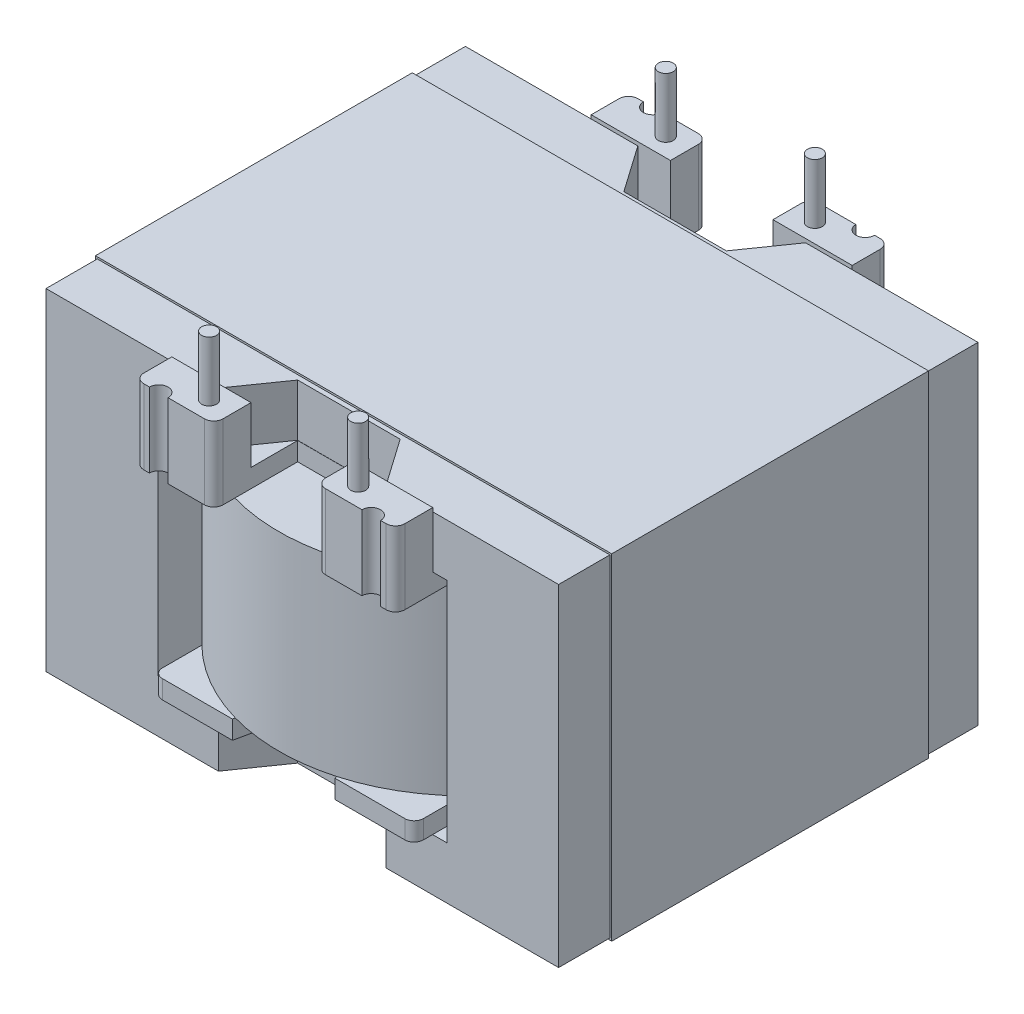
SolidWorks part; units mm, degrees
ref_plane "Спереди" through (0, 0, 0) normal (0, 0, 1) x (1, 0, 0)
ref_plane "Сверху" through (0, 0, 0) normal (0, 1, 0) x (1, 0, 0)
ref_plane "Справа" through (0, 0, 0) normal (1, 0, 0) x (0, 0, -1)
sketch "Эскиз1" plane through (0, 0, 0) normal (0, 1, 0) x (1, 0, 0)
  line L1 (-13.75, -11.25) -> (13.75, -11.25)
  line L2 (-13.75, -11.25) -> (-13.75, 11.25)
  line L3 (-13.75, 11.25) -> (13.75, 11.25)
  line L4 (13.75, -11.25) -> (13.75, 11.25)
  line L5 (-13.75, -11.25) -> (13.75, 11.25) construction
  line L6 (-13.75, 11.25) -> (13.75, -11.25) construction
  point P0 (0, 0)
  dimension "D1" = 27.5
  dimension "D2" = 22.5
extrude "Бобышка-Вытянуть1" add sketch "Эскиз1" along normal blind 17.8
sketch "Эскиз3" plane through (0, 0, 0) normal (0, 0, 1) x (1, 0, 0)
  line L0 (13.75, 17.8) -> (13.75, 0) construction
  line L1 (-7.75, 15) -> (7.75, 15)
  line L2 (-7.75, 15) -> (-7.75, 2.8)
  line L3 (-7.75, 2.8) -> (7.75, 2.8)
  line L4 (7.75, 15) -> (7.75, 2.8)
  line L5 (-7.75, 15) -> (7.75, 2.8) construction
  line L6 (-7.75, 2.8) -> (7.75, 15) construction
  line L7 (13.75, 0) -> (-13.75, 0) construction
  point P0 (0, 8.9)
  point P11 (13.75, 8.9)
  dimension "D1" = 2.8
  dimension "D2" = 15.5
extrude "Вырез-Вытянуть1" cut sketch "Эскиз3" against normal through all both and the other way through all
sketch "Эскиз4" plane through (0, 0, 0) normal (0, 1, 0) x (1, 0, 0)
  line L0 (-4.5, 11.25) -> (-2.75, 8.75)
  line L1 (13.75, 11.25) -> (-13.75, 11.25) construction
  line L2 (-2.75, 8.75) -> (2.75, 8.75)
  line L3 (2.75, 8.75) -> (4.5, 11.25)
  line L4 (4.5, 11.25) -> (-4.5, 11.25)
  line L5 (-18.0038, 0) -> (17.3641, 0) construction
  line L6 (4.5, -11.25) -> (-4.5, -11.25)
  line L7 (2.75, -8.75) -> (4.5, -11.25)
  line L8 (-2.75, -8.75) -> (2.75, -8.75)
  line L9 (-4.5, -11.25) -> (-2.75, -8.75)
  point P4 (0, 8.75)
  point P7 (0, 11.25)
  dimension "D1" = 9
  dimension "D2" = 2.5
  dimension "D3" = 5.5
extrude "Вырез-Вытянуть2" cut sketch "Эскиз4" along normal through all
ref_plane "Плоскость1" through (0, 8.9, 0) normal (0, 1, 0) x (1, 0, 0)
sketch "Эскиз2" plane through (0, 8.9, 0) normal (0, 1, 0) x (1, 0, 0)
  line L0 (0, -2.5) -> (0, 2.5) construction
  line L1 (-10, -2.5) -> (-10, 2.5)
  line L2 (10, -2.5) -> (10, 2.5)
  arc A0 (-10, -2.5) -> (10, -2.5) centre (0, -2.5) ccw
  arc A1 (10, 2.5) -> (-10, 2.5) centre (0, 2.5) ccw
  point P3 (0, 0)
  dimension "D2" = 25
  dimension "D1" = 20
extrude "Бобышка-Вытянуть2" add sketch "Эскиз2" against normal offset from surface 1 and the other way offset from surface 1 up to face at (0, 2.8, 0) other way up to face at (0, 15, 0)
sketch "Эскиз5" plane through (0, 3.8, 0) normal (0, -1, 0) x (1, 0, 0)
  line L0 (7, 11.75) -> (7, -11.75)
  line L1 (6.5, -12.25) -> (2.75, -12.25)
  line L2 (2.75, -12.25) -> (2.0847, -9.1452)
  line L3 (1.5958, -8.75) -> (-1.5958, -8.75)
  line L4 (-2.0847, -9.1452) -> (-2.75, -12.25)
  line L5 (-2.75, -12.25) -> (-6.5, -12.25)
  line L6 (-7, -11.75) -> (-7, 11.75)
  line L10 (7, 0) -> (-7, 0) construction
  line L12 (-2.75, -8.75) -> (2.75, -8.75) construction
  line L13 (-4.5, -11.25) -> (-13.75, -11.25) construction
  line L14 (-2.75, 12.25) -> (-6.5, 12.25)
  line L15 (-2.0847, 9.1452) -> (-2.75, 12.25)
  line L16 (1.5958, 8.75) -> (-1.5958, 8.75)
  line L17 (2.75, 12.25) -> (2.0847, 9.1452)
  line L18 (6.5, 12.25) -> (2.75, 12.25)
  arc A0 (2.0847, -9.1452) -> (1.5958, -8.75) centre (1.5958, -9.25) ccw
  arc A1 (-1.5958, -8.75) -> (-2.0847, -9.1452) centre (-1.5958, -9.25) ccw
  arc A2 (7, -11.75) -> (6.5, -12.25) centre (6.5, -11.75) cw
  arc A3 (-6.5, -12.25) -> (-7, -11.75) centre (-6.5, -11.75) cw
  arc A4 (-6.5, 12.25) -> (-7, 11.75) centre (-6.5, 11.75) ccw
  arc A5 (7, 11.75) -> (6.5, 12.25) centre (6.5, 11.75) ccw
  arc A6 (-1.5958, 8.75) -> (-2.0847, 9.1452) centre (-1.5958, 9.25) cw
  arc A7 (2.0847, 9.1452) -> (1.5958, 8.75) centre (1.5958, 9.25) cw
  point P0 (0, -8.75)
  point P18 (2, -8.75)
  point P21 (-2, -8.75)
  point P40 (-2, 8.75)
  point P41 (2, 8.75)
  dimension "D5" = 0.5
  dimension "D1" = 5.5
  dimension "D2" = 4
  dimension "D3" = 1
  dimension "D4" = 14
extrude "Бобышка-Вытянуть3" add sketch "Эскиз5" along normal offset from surface (0.99 mm away) 0.01 up to face at (0, 2.8, 0)
sketch "Эскиз6" plane through (0, 14, 0) normal (0, 1, 0) x (1, 0, 0)
  line L0 (-7, -12.75) -> (-7, 12.75)
  line L1 (-7, 9.6414) -> (-7, 11.75) construction
  line L2 (-6.5, 13.25) -> (-6.2, 13.25)
  line L3 (-2.75, 12.75) -> (-2.75, 8.75)
  line L4 (-2.75, 8.75) -> (2.75, 8.75)
  line L5 (2.75, 8.75) -> (2.75, 12.75)
  line L6 (3.25, 13.25) -> (5.2, 13.25)
  line L7 (7, 12.75) -> (7, -12.75)
  line L8 (7, 0) -> (-7, 0) construction
  line L9 (13.75, 11.25) -> (4.5, 11.25) construction
  line L10 (-1.5958, 8.75) -> (1.5958, 8.75) construction
  line L11 (0, 8.75) -> (0, -8.75) construction
  line L12 (-5.2, 13.25) -> (-3.25, 13.25)
  line L13 (6.2, 13.25) -> (6.5, 13.25)
  line L14 (6.2, -13.25) -> (6.5, -13.25)
  line L15 (-5.2, -13.25) -> (-3.25, -13.25)
  line L16 (3.25, -13.25) -> (5.2, -13.25)
  line L17 (2.75, -8.75) -> (2.75, -12.75)
  line L18 (-2.75, -8.75) -> (2.75, -8.75)
  line L19 (-2.75, -12.75) -> (-2.75, -8.75)
  line L20 (-6.5, -13.25) -> (-6.2, -13.25)
  arc A0 (-6.2, 13.25) -> (-5.2, 13.25) centre (-5.7, 13.25) ccw
  arc A1 (6.2, 13.25) -> (5.2, 13.25) centre (5.7, 13.25) cw
  arc A2 (-3.25, 13.25) -> (-2.75, 12.75) centre (-3.25, 12.75) cw
  arc A3 (-7, 12.75) -> (-6.5, 13.25) centre (-6.5, 12.75) cw
  arc A4 (6.5, 13.25) -> (7, 12.75) centre (6.5, 12.75) cw
  arc A5 (2.75, 12.75) -> (3.25, 13.25) centre (3.25, 12.75) cw
  arc A6 (2.75, -12.75) -> (3.25, -13.25) centre (3.25, -12.75) ccw
  arc A7 (6.5, -13.25) -> (7, -12.75) centre (6.5, -12.75) ccw
  arc A8 (-7, -12.75) -> (-6.5, -13.25) centre (-6.5, -12.75) ccw
  arc A9 (-3.25, -13.25) -> (-2.75, -12.75) centre (-3.25, -12.75) ccw
  arc A10 (6.2, -13.25) -> (5.2, -13.25) centre (5.7, -13.25) ccw
  arc A11 (-6.2, -13.25) -> (-5.2, -13.25) centre (-5.7, -13.25) cw
  point P0 (0, 8.75)
  point P34 (0, 0)
  dimension "D2" = 0.5
  dimension "D3" = 1.3
  dimension "D4" = 0.5
  dimension "D1" = 2
extrude "Бобышка-Вытянуть4" add sketch "Эскиз6" along normal offset from surface (0.99 mm away) 0.01 up to face at (0, 15, 0)
sketch "Эскиз7" plane through (0, 14.99, 0) normal (0, 1, 0) x (1, 0, 0)
  line L0 (-7, 11.25) -> (-2.75, 11.25)
  line L1 (-4.5, 11.25) -> (-13.75, 11.25) construction
  line L2 (7, 11.25) -> (2.75, 11.25)
  line L3 (13.75, 11.25) -> (4.5, 11.25) construction
  line L4 (7, -11.25) -> (2.75, -11.25)
  line L5 (4.5, -11.25) -> (13.75, -11.25) construction
  line L6 (-7, -11.25) -> (-2.75, -11.25)
  line L7 (-13.75, -11.25) -> (-4.5, -11.25) construction
  line L8 (-7, -11.25) -> (-7, -12.75)
  line L9 (7, 11.25) -> (7, 12.75)
  line L16 (2.75, 12.75) -> (2.75, 8.75)
  line L17 (2.75, 8.75) -> (-2.75, 8.75)
  line L18 (-2.75, 8.75) -> (-2.75, 12.75)
  line L19 (-3.25, 13.25) -> (-5.2, 13.25)
  line L20 (-6.2, 13.25) -> (-6.5, 13.25)
  line L21 (-7, 12.75) -> (-7, -12.75)
  line L22 (-6.5, -13.25) -> (-6.2, -13.25)
  line L23 (-5.2, -13.25) -> (-3.25, -13.25)
  line L24 (-2.75, -12.75) -> (-2.75, -8.75)
  line L25 (-2.75, -8.75) -> (2.75, -8.75)
  line L26 (2.75, -8.75) -> (2.75, -12.75)
  line L27 (3.25, -13.25) -> (5.2, -13.25)
  line L28 (6.2, -13.25) -> (6.5, -13.25)
  line L29 (7, -12.75) -> (7, 12.75)
  line L30 (6.5, 13.25) -> (6.2, 13.25)
  line L31 (5.2, 13.25) -> (3.25, 13.25)
  line L32 (2.75, 12.75) -> (2.75, 11.25)
  line L34 (-2.75, 11.25) -> (-2.75, 12.75)
  line L35 (-3.25, 13.25) -> (-5.2, 13.25)
  line L36 (-6.2, 13.25) -> (-6.5, 13.25)
  line L37 (-7, 12.75) -> (-7, 11.25)
  line L38 (-6.5, -13.25) -> (-6.2, -13.25)
  line L39 (-5.2, -13.25) -> (-3.25, -13.25)
  line L40 (-2.75, -12.75) -> (-2.75, -11.25)
  line L42 (2.75, -11.25) -> (2.75, -12.75)
  line L43 (3.25, -13.25) -> (5.2, -13.25)
  line L44 (6.2, -13.25) -> (6.5, -13.25)
  line L45 (7, -12.75) -> (7, -11.25)
  line L46 (6.5, 13.25) -> (6.2, 13.25)
  line L47 (5.2, 13.25) -> (3.25, 13.25)
  arc A12 (-2.75, 12.75) -> (-3.25, 13.25) centre (-3.25, 12.75) ccw
  arc A13 (-6.2, 13.25) -> (-5.2, 13.25) centre (-5.7, 13.25) ccw
  arc A14 (-6.5, 13.25) -> (-7, 12.75) centre (-6.5, 12.75) ccw
  arc A15 (-7, -12.75) -> (-6.5, -13.25) centre (-6.5, -12.75) ccw
  arc A16 (-5.2, -13.25) -> (-6.2, -13.25) centre (-5.7, -13.25) ccw
  arc A17 (-3.25, -13.25) -> (-2.75, -12.75) centre (-3.25, -12.75) ccw
  arc A18 (2.75, -12.75) -> (3.25, -13.25) centre (3.25, -12.75) ccw
  arc A19 (6.2, -13.25) -> (5.2, -13.25) centre (5.7, -13.25) ccw
  arc A20 (6.5, -13.25) -> (7, -12.75) centre (6.5, -12.75) ccw
  arc A21 (7, 12.75) -> (6.5, 13.25) centre (6.5, 12.75) ccw
  arc A22 (5.2, 13.25) -> (6.2, 13.25) centre (5.7, 13.25) ccw
  arc A23 (3.25, 13.25) -> (2.75, 12.75) centre (3.25, 12.75) ccw
  arc A24 (-2.75, 12.75) -> (-3.25, 13.25) centre (-3.25, 12.75) ccw
  arc A25 (-6.2, 13.25) -> (-5.2, 13.25) centre (-5.7, 13.25) ccw
  arc A26 (-6.5, 13.25) -> (-7, 12.75) centre (-6.5, 12.75) ccw
  arc A27 (-7, -12.75) -> (-6.5, -13.25) centre (-6.5, -12.75) ccw
  arc A28 (-5.2, -13.25) -> (-6.2, -13.25) centre (-5.7, -13.25) ccw
  arc A29 (-3.25, -13.25) -> (-2.75, -12.75) centre (-3.25, -12.75) ccw
  arc A30 (2.75, -12.75) -> (3.25, -13.25) centre (3.25, -12.75) ccw
  arc A31 (6.2, -13.25) -> (5.2, -13.25) centre (5.7, -13.25) ccw
  arc A32 (6.5, -13.25) -> (7, -12.75) centre (6.5, -12.75) ccw
  arc A33 (7, 12.75) -> (6.5, 13.25) centre (6.5, 12.75) ccw
  arc A34 (5.2, 13.25) -> (6.2, 13.25) centre (5.7, 13.25) ccw
  arc A35 (3.25, 13.25) -> (2.75, 12.75) centre (3.25, 12.75) ccw
  dimension "D1" = 0
extrude "Бобышка-Вытянуть5" add sketch "Эскиз7" along normal offset from surface (3.01 mm away) 0.2 up to face at (0, 17.8, 0) offset beyond the face yes
sketch "Эскиз8" plane through (0, 18, 0) normal (0, 1, 0) x (1, 0, 0)
  line L0 (4, -12.25) -> (-4, -12.25) construction
  line L1 (8.5905, 0) -> (-8.5905, 0) construction
  line L2 (-3.25, -13.25) -> (-5.2, -13.25) construction
  circle A0 centre (4, -12.25) radius 0.4
  circle A1 centre (-4, -12.25) radius 0.4
  circle A2 centre (-4, 12.25) radius 0.4
  circle A3 centre (4, 12.25) radius 0.4
  point P6 (0, -12.25)
  dimension "D3" = 0.8
  dimension "D1" = 8
  dimension "D2" = 1
extrude "Бобышка-Вытянуть6" add sketch "Эскиз8" along normal blind 3.2
sketch "Эскиз9" plane through (0, 0, 0) normal (0, 0, 1) x (1, 0, 0)
  line L0 (-13.75, 17.8) -> (-13.75, 0) construction
  line L1 (4.5, 0) -> (13.75, 0) construction
  line L2 (7, 17.8) -> (13.75, 17.8) construction
  line L3 (13.75, 17.8) -> (13.75, 0) construction
  line L4 (-13.75, 17.8) -> (-13.75, 0)
  line L5 (-13.75, 0) -> (13.75, 0)
  line L6 (-13.75, 17.8) -> (13.75, 17.8)
  line L7 (13.75, 17.8) -> (13.75, 0)
  line L8 (-13.85, 17.9) -> (-13.85, -0.1)
  line L9 (-13.85, -0.1) -> (13.85, -0.1)
  line L10 (13.85, 17.9) -> (13.85, -0.1)
  line L11 (-13.85, 17.9) -> (13.85, 17.9)
  dimension "D1" = 0.1
extrude "Бобышка-Вытянуть7" add sketch "Эскиз9" along normal mid plane 17
